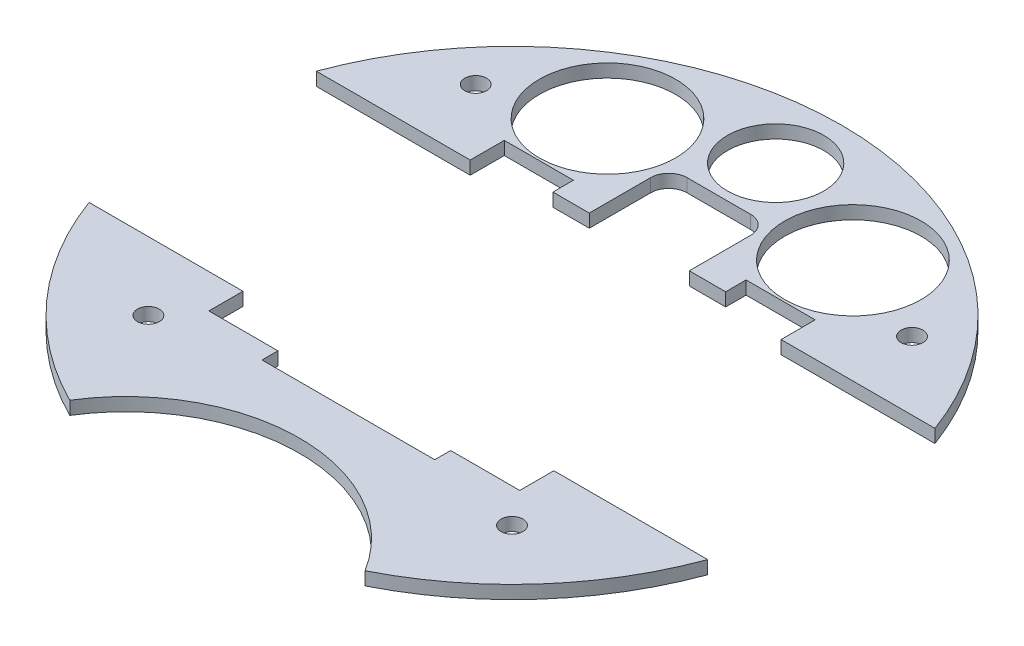
SolidWorks part; units mm, degrees
material "ABS"
ref_plane "Front Plane" through (0, 0, 0) normal (0, 0, 1) x (1, 0, 0)
ref_plane "Top Plane" through (0, 0, 0) normal (0, 1, 0) x (1, 0, 0)
ref_plane "Right Plane" through (0, 0, 0) normal (1, 0, 0) x (0, 0, -1)
sketch "Sketch1" plane through (0, 0, 0) normal (0, 1, 0) x (1, 0, 0)
  line L0 (0, -85) -> (-32.4891, -64.8129) construction
  line L1 (0, -85) -> (0, 0) construction
  arc A0 (32.4891, -64.8129) -> (-32.4891, -64.8129) centre (0, 0) ccw
  arc A1 (32.4891, -64.8129) -> (-32.4891, -64.8129) centre (0, -85) ccw
  dimension "D1" = 145
  dimension "D2" = 76.5
  dimension "D3" = 85
extrude "Boss-Extrude1" add sketch "Sketch1" along normal blind 2.9
sketch "solenoid placement" plane through (0, 2.9, 0) normal (0, 1, 0) x (1, 0, 0)
  line L4 (-19, -36) -> (19, -36)
  line L5 (-19, -36) -> (19, -36)
  line L6 (19, -36) -> (19, 28)
  line L7 (19, -36) -> (19, 28)
  line L8 (19, 28) -> (-19, 28)
  line L9 (19, 28) -> (-19, 28)
  line L10 (-19, 28) -> (-19, -36)
  line L11 (-19, 28) -> (-19, -36)
  circle A1 centre (0, 0) radius 72.5 construction
  arc A2 (32.4891, -64.8129) -> (-32.4891, -64.8129) centre (0, 0) ccw construction
  dimension "D1" = 0
extrude "Cut-Extrude1" cut sketch "solenoid placement" against normal through all
sketch "Sketch3" plane through (0, 2.9, 0) normal (0, 1, 0) x (1, 0, 0)
  circle A1 centre (27, 48) radius 12
  circle A2 centre (-27, 48) radius 12
  dimension "D1" = 24
extrude "Cut-Extrude3" cut sketch "Sketch3" against normal through all
sketch "Sketch4" plane through (0, 2.9, 0) normal (0, 1, 0) x (1, 0, 0)
  circle A2 centre (40, -40) radius 2.4
  circle A3 centre (40, -40) radius 2.4
  circle A4 centre (-40, -40) radius 2.4
  circle A5 centre (-40, -40) radius 2.4
  circle A6 centre (48, 40) radius 2.4
  circle A7 centre (48, 40) radius 2.4
  circle A8 centre (-48, 40) radius 2.4
  circle A12 centre (-48, 40) radius 2.4
  dimension "D1" = 0
  dimension "D2" = 0
  dimension "D3" = 0
  dimension "D4" = 0
extrude "Cut-Extrude4" cut sketch "Sketch4" against normal through all
sketch "Sketch2" plane through (0, 2.9, 0) normal (0, 1, 0) x (1, 0, 0)
  line L9 (-34.2, -32.5) -> (-22.2, -32.5)
  line L10 (-22.2, -32.5) -> (-19, -32.5)
  line L11 (-19, -32.5) -> (-19, 32.5)
  line L12 (-19, 32.5) -> (-22.2, 32.5)
  line L13 (-22.2, 32.5) -> (-34.2, 32.5)
  line L14 (-34.2, 32.5) -> (-34.2, 25)
  line L15 (-34.2, 25) -> (-68.0533, 25)
  line L16 (-68.0533, -25) -> (-34.2, -25)
  line L17 (-34.2, -25) -> (-34.2, -32.5)
  line L18 (-34.2, -32.5) -> (-22.2, -32.5)
  line L19 (-22.2, -32.5) -> (-19, -32.5)
  line L20 (-19, -32.5) -> (-19, 32.5)
  line L21 (-19, 32.5) -> (-22.2, 32.5)
  line L22 (-22.2, 32.5) -> (-34.2, 32.5)
  line L23 (-34.2, 32.5) -> (-34.2, 25)
  line L24 (-34.2, 25) -> (-68.0533, 25)
  line L25 (-68.0533, -25) -> (-34.2, -25)
  line L26 (-34.2, -25) -> (-34.2, -32.5)
  line L27 (19, 32.5) -> (19, -32.5)
  line L28 (19, -32.5) -> (22.2, -32.5)
  line L29 (22.2, -32.5) -> (34.2, -32.5)
  line L30 (34.2, -32.5) -> (34.2, -25)
  line L31 (34.2, -25) -> (68.0533, -25)
  line L32 (68.0533, 25) -> (34.2, 25)
  line L33 (34.2, 25) -> (34.2, 32.5)
  line L34 (34.2, 32.5) -> (22.2, 32.5)
  line L35 (22.2, 32.5) -> (19, 32.5)
  line L36 (19, 32.5) -> (19, -32.5)
  line L37 (19, -32.5) -> (22.2, -32.5)
  line L38 (22.2, -32.5) -> (34.2, -32.5)
  line L39 (34.2, -32.5) -> (34.2, -25)
  line L40 (34.2, -25) -> (68.0533, -25)
  line L41 (68.0533, 25) -> (34.2, 25)
  line L42 (34.2, 25) -> (34.2, 32.5)
  line L43 (34.2, 32.5) -> (22.2, 32.5)
  line L44 (22.2, 32.5) -> (19, 32.5)
  arc A2 (-68.0533, 25) -> (-68.0533, -25) centre (0, 0) ccw
  arc A3 (-68.0533, 25) -> (-68.0533, -25) centre (0, 0) ccw
  arc A4 (68.0533, -25) -> (68.0533, 25) centre (0, 0) ccw
  arc A5 (68.0533, -25) -> (68.0533, 25) centre (0, 0) ccw
  dimension "D2" = 0
  dimension "D1" = 0
extrude "Cut-Extrude2" cut sketch "Sketch2" against normal through all
sketch "Sketch5" plane through (0, 2.9, 0) normal (0, 1, 0) x (1, 0, 0)
  line L8 (-11, 28) -> (11, 28)
  line L9 (11, 28) -> (11, 41.5)
  line L10 (7, 45.5) -> (-7, 45.5)
  line L11 (-11, 41.5) -> (-11, 28)
  line L12 (19, 28) -> (-19, 28) construction
  arc A4 (11, 41.5) -> (7, 45.5) centre (7, 41.5) ccw
  arc A5 (-7, 45.5) -> (-11, 41.5) centre (-7, 41.5) ccw
  point P10 (0, 28)
  point P13 (0, 28)
  line M18 (-19, 28) -> (19, 28)
  dimension "D3" = 4
  dimension "D1" = 22
  dimension "D2" = 17.5
extrude "Cut-Extrude5" cut sketch "Sketch5" against normal through all contours L10 A5 L11 L9 A4 M18 region at (0, 2.9, -36.6073)
sketch "Sketch6" plane through (0, 2.9, 0) normal (0, 1, 0) x (-1, 0, 0)
  circle A1 centre (-27, -48) radius 15
  circle A2 centre (-27, -48) radius 15
  circle A3 centre (27, -48) radius 15
  circle A4 centre (27, -48) radius 15
  dimension "D1" = 0
  dimension "D2" = 0
extrude "Cut-Extrude10" cut sketch "Sketch6" against normal through all
sketch "Sketch7" plane through (0, 2.9, 0) normal (0, 1, 0) x (1, 0, 0)
  circle A1 centre (0, 58) radius 10.605
  circle A2 centre (0, 58) radius 10.605
  dimension "D1" = 0
extrude "Cut-Extrude11" cut sketch "Sketch7" against normal through all
equation "\"smallPulleyTeeth\"= 15"
equation "\"largePulleyTeeth\"= 30"
equation "\"eighthThick\"= 2.9mm"
equation "\"sixteenthThick\" = 1.7mm"
equation "\"quarterThick\"=6.0mm"
equation "\"OD\" = 145mm"
equation "\"puckAngle\" = 60.5deg"
equation "\"D1@Sketch1\"=\"OD\""
equation "\"puckDiam\" = 76.5mm"
equation "\"D2@Sketch1\"=\"puckDiam\""
equation "\"D1@Boss-Extrude1\"=\"eighthThick\""
equation "\"axlePress\" = 5.9mm"
equation "\"press\" = 0.2mm"
equation "\"wheelClear\" = 0.3mm"
equation "\"10-32clear\" = 4.8mm"
equation "\"6-32clear\" = 3.3mm"
equation "\"8-32clear\" = 4.0mm"
equation "\"wheelHeight\" = 22mm"
equation "\"wheelWell\" = 65mm"
equation "\"puckDist\" = 85mm"
equation "\"scoopFillet\" = 5mm"
equation "\"4-40clear\" = 3.0mm"
equation "\"D3@Sketch1\"=\"puckDist\""
